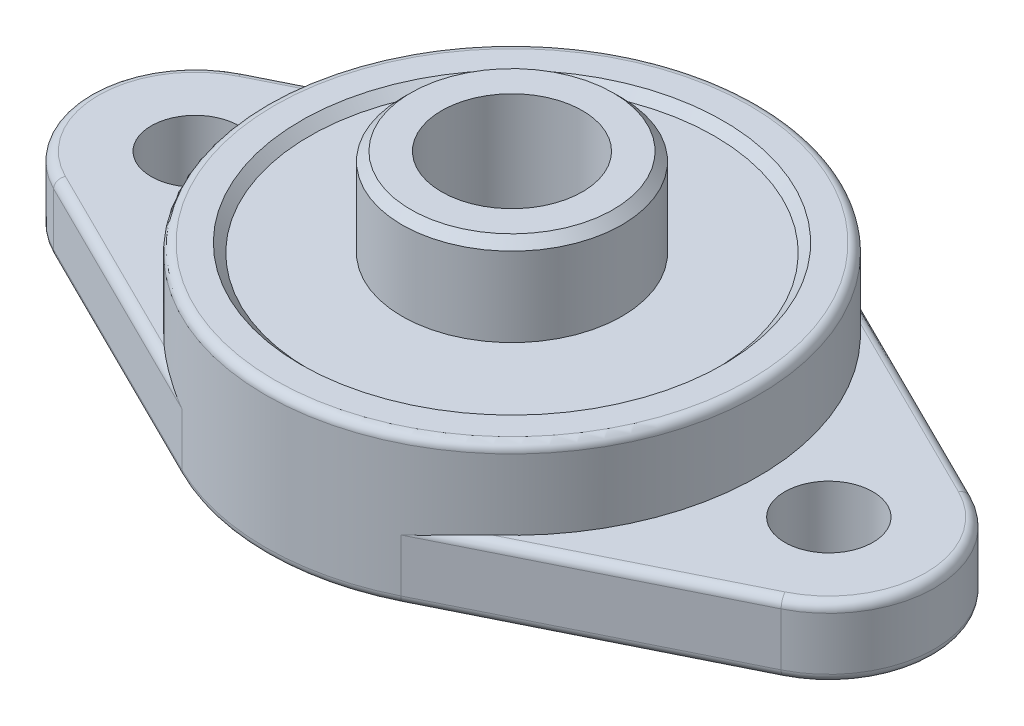
SolidWorks part; units mm, degrees
ref_plane "Front Plane" through (0, 0, 0) normal (0, 0, 1) x (1, 0, 0)
ref_plane "Top Plane" through (0, 0, 0) normal (0, 1, 0) x (1, 0, 0)
ref_plane "Right Plane" through (0, 0, 0) normal (1, 0, 0) x (0, 0, -1)
sketch "Sketch1" plane through (0, 0, 0) normal (0, 1, 0) x (1, 0, 0)
  line L0 (0, 0) -> (0, -21.8376) construction
  line L1 (-24, 14) -> (24, 14) construction
  line L2 (-24, 14) -> (-24, -14) construction
  line L3 (-24, -14) -> (24, -14) construction
  line L4 (24, 14) -> (24, -14) construction
  line L5 (-24, 14) -> (24, -14) construction
  line L6 (-24, -14) -> (24, 14) construction
  line L7 (-20.6667, 5.3748) -> (-6.2222, 12.5413)
  line L8 (-20.6667, -5.3748) -> (-6.2222, -12.5413)
  line L9 (0, 0) -> (30.335, 0) construction
  line L10 (20.6667, -5.3748) -> (6.2222, -12.5413)
  line L11 (20.6667, 5.3748) -> (6.2222, 12.5413)
  circle A0 centre (-18, 0) radius 2.5
  arc A1 (-20.6667, -5.3748) -> (-20.6667, 5.3748) centre (-18, 0) cw
  arc A2 (-6.2222, -12.5413) -> (6.2222, -12.5413) centre (0, 0) ccw
  circle A3 centre (-18, 0) radius 6 construction
  circle A4 centre (0, 0) radius 14 construction
  arc A5 (-6.2222, 12.5413) -> (6.2222, 12.5413) centre (0, 0) cw
  arc A6 (20.6667, -5.3748) -> (20.6667, 5.3748) centre (18, 0) ccw
  circle A7 centre (18, 0) radius 2.5
  point P0 (0, 0)
  dimension "D4" = 5
  dimension "D5" = 3.5
  dimension "D1" = 48
  dimension "D2" = 28
  dimension "D3" = 18
extrude "Boss-Extrude1" add sketch "Sketch1" along normal blind 4
sketch "Sketch2" plane through (0, 4, 0) normal (0, 1, 0) x (1, 0, 0)
  circle A0 centre (0, 0) radius 14
extrude "Boss-Extrude2" add sketch "Sketch2" along normal blind 4.5
sketch "Sketch3" plane through (0, 8.5, 0) normal (0, 1, 0) x (1, 0, 0)
  circle A0 centre (0, 0) radius 6.25
  dimension "D1" = 12.5
extrude "Boss-Extrude3" add sketch "Sketch3" along normal blind 13 from surface starting at face at (-18, 0, 2.5)
sketch "Sketch4" plane through (0, 13, 0) normal (0, 1, 0) x (1, 0, 0)
  circle A0 centre (0, 0) radius 4
  dimension "D1" = 8
extrude "Cut-Extrude1" cut sketch "Sketch4" against normal through all
fillet "Fillet1" radius 0.5 15 edges at (0, 0, 14) (-13.4444, 0, 8.9581) (-24, 0, 0) (-13.4444, 0, -8.9581) (0, 0, -14) (13.4444, 0, -8.9581) (24, 0, 0) (13.4444, 4, -8.9581) (24, 4, 0) (-13.4444, 4, -8.9581) (-24, 4, 0) (13.4444, 0, 8.9581) (13.4444, 4, 8.9581) (0, 8.5, 14) (-13.4444, 4, 8.9581)
chamfer "Chamfer1" distance 0.5 angle 45 1 edges at (0, 13, -6.25)
sketch "Sketch5" plane through (0, 8.5, 0) normal (0, 1, 0) x (1, 0, 0)
  circle A0 centre (0, 0) radius 11.5
  circle A1 centre (0, 0) radius 6.25
  circle A2 centre (0, 0) radius 6.25 construction
  circle A3 centre (0, 0) radius 14 construction
  dimension "D1" = 2.5
extrude "Cut-Extrude2" cut sketch "Sketch5" against normal blind 0.5
chamfer "Chamfer2" distance 0.5 angle 45 1 edges at (0, 8.5, 11.5)
